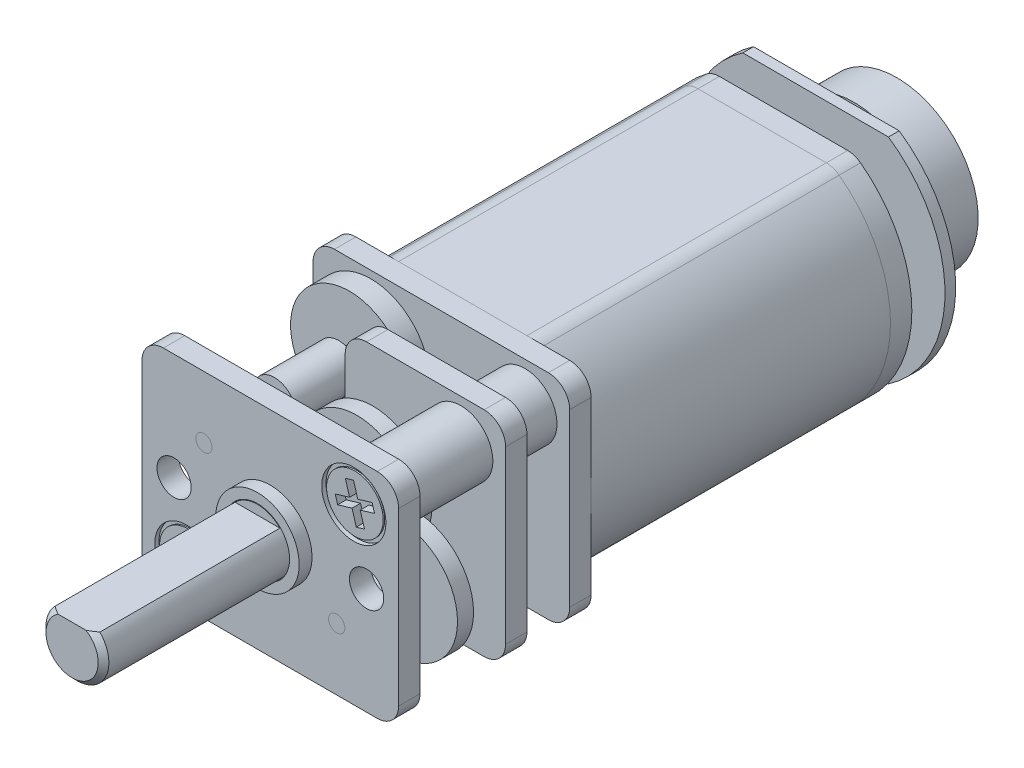
SolidWorks part; units mm, degrees
note: The reader was unsure of these and kept them because the rebuilt part matched: shared geometry of "Sketch2<2>", "Sketch9<3>", "Sketch12<2>", "Sketch29<3>".
material "Plain Carbon Steel"
ref_plane "Front Plane" through (0, 0, 0) normal (0, 0, 1) x (1, 0, 0)
ref_plane "Top Plane" through (0, 0, 0) normal (0, 1, 0) x (1, 0, 0)
ref_plane "Right Plane" through (0, 0, 0) normal (1, 0, 0) x (0, 0, -1)
sketch "Sketch1" plane through (0, 0, 0) normal (0, 0, 1) x (1, 0, 0)
  line L0 (3.3166, 5) -> (-3.3166, 5)
  line L1 (-3.3166, -5) -> (3.3166, -5)
  arc A0 (3.3166, -5) -> (3.3166, 5) centre (0, 0) ccw
  arc A1 (-3.3166, 5) -> (-3.3166, -5) centre (0, 0) ccw
  dimension "D1" = 12
  dimension "D2" = 10
extrude "Boss-Extrude1" add sketch "Sketch1" along normal mid plane 15
fillet "Fillet3" radius 1 4 edges at (-3.3166, -5, 0) (3.3166, -5, 0) (3.3166, 5, 0) (-3.3166, 5, 0)
sketch "Sketch2" plane through (0, 0, 7.5) normal (0, 0, 1) x (1, 0, 0)
  line L1 (-5, -5) -> (5, -5)
  line L2 (-6, -4) -> (-6, 4)
  line L3 (-5, 5) -> (5, 5)
  line L4 (6, -4) -> (6, 4)
  line L5 (-6, -5) -> (6, 5) construction
  line L6 (-6, 5) -> (6, -5) construction
  arc A0 (-5, -5) -> (-6, -4) centre (-5, -4) cw
  arc A1 (5, -5) -> (6, -4) centre (5, -4) ccw
  arc A2 (5, 5) -> (6, 4) centre (5, 4) cw
  arc A3 (-6, 4) -> (-5, 5) centre (-5, 4) cw
  point P0 (0, 0)
  dimension "D3" = 1
  dimension "D1" = 12
  dimension "D2" = 10
extrude "Boss-Extrude2" add sketch "Sketch2" along normal blind 1 separate body
extrude "Boss-Extrude3" add sketch "Sketch2<2>" against normal blind 1 from offset 9 separate body
sketch "Sketch2<2>" plane through (0, 0, 7.5) normal (0, 0, 1) x (1, 0, 0) same geometry as "Sketch2"
sketch "Sketch7" plane through (0, 0, 8.5) normal (0, 0, 1) x (1, 0, 0)
  line L0 (-3.1041, 2.1041) -> (3.1041, -2.1041) construction
  line L1 (0, 0) -> (0, 50000) construction
  line L2 (-6, 4) -> (-6, -4) construction
  line L3 (5, 5) -> (-5, 5) construction
  circle A0 centre (0, 0) radius 3.75 construction
  circle A1 centre (-3.1041, 2.1041) radius 0.5
  circle A2 centre (3.1041, -2.1041) radius 0.5
  circle A3 centre (-3.1041, 2.1041) radius 2.8959 construction
  point P3 (3.1041, -2.1041)
  point P4 (-3.1041, 2.1041)
  dimension "D1" = 7.5
  dimension "D3" = 1
extrude "Boss-Extrude5" add sketch "Sketch7" along normal up to surface (8 mm away) separate body up to face at (0, 0, 16.5)
sketch "Sketch11" plane through (0, 0, 8.5) normal (0, 0, 1) x (1, 0, 0)
  line L0 (-5, -1.25) -> (-2.5, -1.25)
  line L1 (-1.5, -0.25) -> (-1.5, 4)
  line L4 (-5, -5) -> (5, -5)
  line L5 (6, -4) -> (6, 4)
  line L6 (5, 5) -> (-5, 5)
  line L7 (-6, 4) -> (-6, -4)
  line L8 (-5, -5) -> (5, -5)
  line L9 (6, -4) -> (6, 4)
  line L10 (5, 5) -> (-0.5, 5)
  line L11 (-6, -2.25) -> (-6, -4)
  arc A0 (-1.5, 4) -> (-0.5, 5) centre (-0.5, 4) cw
  arc A1 (-2.5, -1.25) -> (-1.5, -0.25) centre (-2.5, -0.25) ccw
  arc A2 (-5, -1.25) -> (-6, -2.25) centre (-5, -2.25) ccw
  arc A4 (-6, -4) -> (-5, -5) centre (-5, -4) ccw
  arc A5 (5, -5) -> (6, -4) centre (5, -4) ccw
  arc A6 (6, 4) -> (5, 5) centre (5, 4) ccw
  arc A7 (-5, 5) -> (-6, 4) centre (-5, 4) ccw
  arc A8 (-6, -4) -> (-5, -5) centre (-5, -4) ccw
  arc A9 (5, -5) -> (6, -4) centre (5, -4) ccw
  arc A10 (6, 4) -> (5, 5) centre (5, 4) ccw
  dimension "D2" = 1
  dimension "D3" = 7.5
  dimension "D4" = 3.75
  dimension "D1" = 0
extrude "Boss-Extrude8" add sketch "Sketch11" along normal blind 1 from offset 2 separate body
sketch "Sketch5" plane through (0, 0, 16.5) normal (0, 0, 1) x (1, 0, 0)
  line L0 (5, 4) -> (-5, -4) construction
  circle A0 centre (0, 0) radius 0.75
  circle A1 centre (-3.1041, 2.1041) radius 0.38
  circle A2 centre (3.1041, -2.1041) radius 0.38
  circle A3 centre (0, 0) radius 5 construction
  circle A4 centre (3.9043, 3.1235) radius 0.75
  circle A5 centre (-3.9043, -3.1235) radius 0.75
  circle A6 centre (0, 0) radius 5.75 construction
  dimension "D1" = 1.5
  dimension "D2" = 0.76
  dimension "D3" = 11.5
  dimension "D4" = 1.5
extrude "Cut-Extrude1" cut sketch "Sketch5" against normal up to surface (9 mm away)
sketch "Sketch8" plane through (0, 0, 16.5) normal (0, 0, 1) x (1, 0, 0)
  circle A0 centre (-3.1041, 2.1041) radius 0.5
  circle A1 centre (3.1041, -2.1041) radius 0.5
  circle A2 centre (-3.1041, 2.1041) radius 0.5 construction
  circle A3 centre (-3.1041, 2.1041) radius 0.38
  circle A4 centre (3.1041, -2.1041) radius 0.38
  circle A5 centre (-3.1041, 2.1041) radius 0.38 construction
extrude "Cut-Extrude2" cut sketch "Sketch8" against normal blind 1
sketch "Sketch9" plane through (0, 0, 8.5) normal (0, 0, 1) x (1, 0, 0)
  circle A0 centre (-3.1041, 2.1041) radius 2.75
  circle A1 centre (-3.1041, 2.1041) radius 0.5
  circle A2 centre (-3.1041, 2.1041) radius 0.5 construction
  circle A3 centre (0, 0) radius 1
  circle M1 centre (0, 0) radius 0.75
  dimension "D1" = 5.5
  dimension "D2" = 2
extrude "Boss-Extrude6" add sketch "Sketch9" along normal blind 1 from offset 0.2 separate body contours A0 A1
extrude "Boss-Extrude16" add sketch "Sketch9<3>" along normal blind 1.3 from offset 0.1 separate body contours A3 M1 | M1
sketch "Sketch9<3>" plane through (0, 0, 8.5) normal (0, 0, 1) x (1, 0, 0) same geometry as "Sketch9"
sketch "Sketch6" plane through (0, 0, 16.5) normal (0, 0, 1) x (1, 0, 0)
  circle A0 centre (0, 0) radius 1.95
  circle A1 centre (0, 0) radius 0.75
  circle A2 centre (0, 0) radius 0.75 construction
  dimension "D1" = 3.9
extrude "Boss-Extrude4" add sketch "Sketch6" along normal blind 0.6
sketch "Sketch10" plane through (0, 0, 9.7) normal (0, 0, 1) x (1, 0, 0)
  circle A0 centre (-3.1041, 2.1041) radius 0.5
  circle A1 centre (-3.1041, 2.1041) radius 1
  circle A2 centre (0, 0) radius 2.75 construction
  circle A4 centre (-3.1041, 2.1041) radius 0.5 construction
  circle A5 centre (-3.1041, 2.1041) radius 2.75 construction
extrude "Boss-Extrude7" add sketch "Sketch10" along normal blind 3 from offset 0.5 separate body
sketch "Sketch12" plane through (0, 0, 8.5) normal (0, 0, 1) x (1, 0, 0)
  circle A0 centre (-3.9043, -3.1235) radius 0.75
  circle A1 centre (-3.9043, -3.1235) radius 1.5
  circle A2 centre (-3.9043, -3.1235) radius 0.75 construction
  circle A3 centre (3.9043, 3.1235) radius 0.75
  circle A4 centre (3.9043, 3.1235) radius 1.5
  dimension "D1" = 3
extrude "Boss-Extrude9" add sketch "Sketch12" along normal up to next (2 mm away) separate body
extrude "Boss-Extrude10" add sketch "Sketch12<2>" along normal up to next (7 mm away) from surface at 3 separate body starting at face at (0.75, 0, 11.5)
sketch "Sketch12<2>" plane through (0, 0, 8.5) normal (0, 0, 1) x (1, 0, 0) same geometry as "Sketch12"
sketch "Sketch13" plane through (0, 0, 17.1) normal (0, 0, 1) x (1, 0, 0)
  circle A0 centre (0, 0) radius 1.5
  dimension "D1" = 3
extrude "Cut-Extrude3" cut sketch "Sketch13" against normal up to next (7.2 mm away)
sketch "Sketch14" plane through (0, 0, 16.5) normal (0, 0, 1) x (1, 0, 0)
  circle A0 centre (3.9043, 3.1235) radius 1.5
  circle A1 centre (-3.9043, -3.1235) radius 1.5
  dimension "D1" = 3
extrude "Cut-Extrude4" cut sketch "Sketch14" against normal blind 0.2
chamfer "Chamfer1" distance 0.5 angle 45 2 edges at (-3.1543, -3.1235, 16.3) (4.6543, 3.1235, 16.3)
sketch "Sketch15" plane through (0, 0, 11.5) normal (0, 0, 1) x (1, 0, 0)
  circle A0 centre (0, 0) radius 2.75
  circle A1 centre (-3.1041, 2.1041) radius 1 construction
extrude "Boss-Extrude11" add sketch "Sketch15" along normal blind 0.75 from offset 0.2 separate body
sketch "Sketch16" plane through (0, 0, 12.45) normal (0, 0, 1) x (1, 0, 0)
  circle A0 centre (0, 0) radius 1
  circle A2 centre (0, 0) radius 1 construction
extrude "Boss-Extrude12" add sketch "Sketch16" along normal blind 1.15 from offset 0.2
sketch "Sketch17" plane through (0, 0, 12.45) normal (0, 0, 1) x (1, 0, 0)
  circle A0 centre (3.1041, -2.1041) radius 2.75
  circle A2 centre (0, 0) radius 1 construction
extrude "Boss-Extrude13" add sketch "Sketch17" along normal blind 0.75 from offset 0.4 separate body
sketch "Sketch18" plane through (0, 0, 13.6) normal (0, 0, 1) x (1, 0, 0)
  circle A0 centre (3.1041, -2.1041) radius 1
  circle A1 centre (0, 0) radius 1 construction
extrude "Boss-Extrude14" add sketch "Sketch18" along normal blind 1.5 from offset 0.2
sketch "Sketch19" plane through (0, 0, 15.3) normal (0, 0, 1) x (1, 0, 0)
  circle A0 centre (3.1041, -2.1041) radius 0.5
  circle A1 centre (3.1041, -2.1041) radius 0.5 construction
extrude "Cut-Extrude5" cut sketch "Sketch19" against normal through all
sketch "Sketch20" plane through (0, 0, 15.3) normal (0, 0, 1) x (1, 0, 0)
  circle A0 centre (0, 0) radius 2.75
  circle A1 centre (3.1041, -2.1041) radius 1 construction
extrude "Boss-Extrude15" add sketch "Sketch20" against normal blind 1 separate body
sketch "Sketch21" plane through (0, 0, 15.3) normal (0, 0, 1) x (1, 0, 0)
  circle A0 centre (0, 0) radius 0.5
  dimension "D1" = 1
extrude "Cut-Extrude6" cut sketch "Sketch21" against normal up to surface (7.8 mm away)
sketch "Sketch22" plane through (0, 0, 0) normal (0, 1, 0) x (1, 0, 0)
  line L0 (0, 0) -> (0, -50000) construction
  line L1 (-3, 7.5) -> (3, 7.5) construction
  line L2 (-0.5, -7.5) -> (-0.5, -15.3)
  line L3 (0.75, -7.5) -> (-0.75, -7.5) construction
  line L4 (-0.5, -15.3) -> (0.5, -15.3) construction
  line L5 (-0.5, -15.3) -> (-1.47, -15.3)
  line L6 (-2.75, -15.3) -> (2.75, -15.3) construction
  line L7 (-1.47, -15.3) -> (-1.47, -25.77)
  line L8 (-1.47, -25.77) -> (0, -25.77)
  line L9 (0, -25.77) -> (0, -7.5)
  line L10 (3, -7.5) -> (-3, -7.5) construction
  line L11 (0, -7.5) -> (-0.5, -7.5)
  line L12 (5, -16.5) -> (-5, -16.5) construction
  point P4 (0, 7.5)
  dimension "D1" = 1
  dimension "D2" = 2.94
  dimension "D3" = 9.27
revolve "Revolve1" add sketch "Sketch22" angle 360 about L0
chamfer "Chamfer2" distance 0.25 angle 45 1 edges at (-1.47, 0, 25.77)
sketch "Sketch23" plane through (0, 0, 25.77) normal (0, 0, 1) x (1, 0, 0)
  line L0 (1.0488, 1.03) -> (-1.0488, 1.03)
  circle A0 centre (0, 0) radius 1.47 construction
  arc A1 (1.0488, 1.03) -> (-1.0488, 1.03) centre (0, 0) ccw
  point P4 (0, -1.47)
  dimension "D1" = 2.5
extrude "Cut-Extrude7" cut sketch "Sketch23" against normal up to surface (8.67 mm away) up to face at (1.5, 0, 17.1)
sketch "Sketch24" plane through (0, 0, 16.5) normal (0, 0, 1) x (1, 0, 0)
  circle A0 centre (4.5, 0) radius 0.8
  circle A1 centre (-4.5, 0) radius 0.8
  dimension "D3" = 1.6
  dimension "D1" = 4.5
  dimension "D2" = 9
extrude "Cut-Extrude8" cut sketch "Sketch24" against normal up to next (1 mm away)
sketch "Sketch25" plane through (0, 0, -7.5) normal (0, 0, -1) x (-1, 0, 0)
  line L2 (-3, -5) -> (3, -5)
  line L3 (3, 5) -> (-3, 5)
  line L4 (-3, -5) -> (3, -5)
  line L5 (3, 5) -> (-3, 5)
  arc A2 (-3.6, 4.8) -> (-3.6, -4.8) centre (0, 0) ccw
  arc A3 (3.6, -4.8) -> (3.6, 4.8) centre (0, 0) ccw
  arc A4 (-3.6, 4.8) -> (-3.6, -4.8) centre (0, 0) ccw
  arc A5 (3.6, -4.8) -> (3.6, 4.8) centre (0, 0) ccw
  arc A10 (3, -5) -> (3.6, -4.8) centre (3, -4) ccw
  arc A11 (3, -5) -> (3.6, -4.8) centre (3, -4) ccw
  arc A12 (3.6, 4.8) -> (3, 5) centre (3, 4) ccw
  arc A13 (3.6, 4.8) -> (3, 5) centre (3, 4) ccw
  arc A14 (-3, 5) -> (-3.6, 4.8) centre (-3, 4) ccw
  arc A15 (-3, 5) -> (-3.6, 4.8) centre (-3, 4) ccw
  arc A16 (-3.6, -4.8) -> (-3, -5) centre (-3, -4) ccw
  arc A17 (-3.6, -4.8) -> (-3, -5) centre (-3, -4) ccw
  dimension "D1" = 0
extrude "Cut-Extrude9" cut sketch "Sketch25" against normal blind 1
sketch "Sketch26" plane through (0, 0, -6.5) normal (0, 0, -1) x (-1, 0, 0)
  line L2 (-3, -5) -> (3, -5)
  line L3 (3, 5) -> (-3, 5)
  line L4 (-3, -5) -> (3, -5)
  line L5 (3, 5) -> (-3, 5)
  arc A2 (-3.6, 4.8) -> (-3.6, -4.8) centre (0, 0) ccw
  arc A3 (3.6, -4.8) -> (3.6, 4.8) centre (0, 0) ccw
  arc A4 (-3.6, 4.8) -> (-3.6, -4.8) centre (0, 0) ccw
  arc A5 (3.6, -4.8) -> (3.6, 4.8) centre (0, 0) ccw
  arc A10 (-3.6, -4.8) -> (-3, -5) centre (-3, -4) ccw
  arc A11 (-3.6, -4.8) -> (-3, -5) centre (-3, -4) ccw
  arc A12 (3, -5) -> (3.6, -4.8) centre (3, -4) ccw
  arc A13 (3, -5) -> (3.6, -4.8) centre (3, -4) ccw
  arc A14 (3.6, 4.8) -> (3, 5) centre (3, 4) ccw
  arc A15 (3.6, 4.8) -> (3, 5) centre (3, 4) ccw
  arc A16 (-3, 5) -> (-3.6, 4.8) centre (-3, 4) ccw
  arc A17 (-3, 5) -> (-3.6, 4.8) centre (-3, 4) ccw
  dimension "D1" = 0
extrude "Boss-Extrude17" add sketch "Sketch26" along normal blind 1 separate body
sketch "Sketch27" plane through (0, 0, -7.5) normal (0, 0, -1) x (-1, 0, 0)
  circle A0 centre (0, 0) radius 2.5
  dimension "D1" = 5
extrude "Boss-Extrude18" add sketch "Sketch27" along normal blind 1.5
sketch "Sketch28" plane through (0, 0, -7.5) normal (0, 0, -1) x (-1, 0, 0)
  line L1 (3.35, 0.75) -> (3.65, 0.75)
  line L2 (3.35, 0.75) -> (3.35, -0.75)
  line L3 (3.35, -0.75) -> (3.65, -0.75)
  line L4 (3.65, 0.75) -> (3.65, -0.75)
  line L5 (3.35, 0.75) -> (3.65, -0.75) construction
  line L6 (3.35, -0.75) -> (3.65, 0.75) construction
  line L7 (-3.65, 0.75) -> (-3.35, 0.75)
  line L8 (-3.65, 0.75) -> (-3.65, -0.75)
  line L9 (-3.65, -0.75) -> (-3.35, -0.75)
  line L10 (-3.35, 0.75) -> (-3.35, -0.75)
  line L11 (-3.65, 0.75) -> (-3.35, -0.75) construction
  line L12 (-3.65, -0.75) -> (-3.35, 0.75) construction
  point P0 (3.5, 0)
  point P5 (-3.5, 0)
  dimension "D1" = 3.5
  dimension "D2" = 7
  dimension "D3" = 0.3
  dimension "D4" = 1.5
extrude "Boss-Extrude19" add sketch "Sketch28" along normal blind 2 separate body
fillet "Fillet1" radius 0.7 2 edges at (-3.5, -0.75, -9.5) (-3.5, 0.75, -9.5)
fillet "Fillet2" radius 0.7 2 edges at (3.5, -0.75, -9.5) (3.5, 0.75, -9.5)
ref_plane "Plane1" through (0, 0, 0) normal (0.6247, -0.7809, 0) x (0.7809, 0.6247, 0)
sketch "Sketch29" plane through (0, 0, 0) normal (0.6247, -0.7809, 0) x (0.7809, 0.6247, 0)
  line L0 (5, 16.5) -> (5, 50016.5) construction
  line L1 (6.5, 16.5) -> (3.5, 16.5) construction
  line L2 (-5, 16.5) -> (-5, 50016.5) construction
  line L3 (-3.5, 16.5) -> (-6.5, 16.5) construction
  line L4 (5.7, 7.5) -> (5.7, 15.755)
  line L5 (6, 7.5) -> (-0.1874, 7.5) construction
  line L6 (5.7, 15.755) -> (6.325, 16.38)
  line L7 (6.325, 16.38) -> (6.325, 16.45)
  line L8 (6.325, 16.45) -> (5, 16.45)
  line L9 (5, 16.45) -> (5, 7.5)
  line L10 (4.25, 7.5) -> (5.75, 7.5) construction
  line L11 (5, 7.5) -> (5.7, 7.5)
  line L12 (2.1864, 16.5) -> (7.184, 16.5) construction
  line L13 (0, 0) -> (0, 50000) construction
  line L14 (-5, 7.5) -> (-5.7, 7.5)
  line L15 (-5, 16.45) -> (-5, 7.5)
  line L16 (-6.325, 16.45) -> (-5, 16.45)
  line L17 (-6.325, 16.38) -> (-6.325, 16.45)
  line L18 (-5.7, 15.755) -> (-6.325, 16.38)
  line L19 (-5.7, 7.5) -> (-5.7, 15.755)
  point P4 (5, 16.5)
  point P9 (-5, 16.5)
  dimension "D1" = 45
  dimension "D2" = 1.4
  dimension "D3" = 2.65
  dimension "D4" = 0.05
  dimension "D5" = 0.07
revolve "Revolve2" add sketch "Sketch29" angle 360 about L0
revolve "Revolve3" add sketch "Sketch29<3>" angle 360 about L2
sketch "Sketch29<3>" plane through (0, 0, 0) normal (0.6247, -0.7809, 0) x (0.7809, 0.6247, 0) same geometry as "Sketch29"
sketch "Sketch30" plane through (0, 0, 16.45) normal (0, 0, 1) x (1, 0, 0)
  line L0 (-3.5871, -2.2813) -> (-4.2216, -3.9657) construction
  line L1 (-3.7742, -2.2107) -> (-4.021, -2.8658)
  line L2 (-4.7466, -2.8062) -> (-3.0621, -3.4408) construction
  line L3 (-4.8171, -2.9934) -> (-4.162, -3.2401)
  line L4 (-3.3999, -2.3518) -> (-3.6467, -3.0068)
  line L5 (-4.6761, -2.619) -> (-4.021, -2.8658)
  line L6 (-3.7742, -2.2107) -> (-3.3999, -2.3518)
  line L7 (-4.4088, -3.8952) -> (-4.0345, -4.0362)
  line L8 (-4.8171, -2.9934) -> (-4.6761, -2.619)
  line L9 (-3.1326, -3.6279) -> (-2.9916, -3.2536)
  line L10 (-4.162, -3.2401) -> (-4.4088, -3.8952)
  line L11 (-3.7742, -2.2107) -> (-4.4088, -3.8952) construction
  line L12 (-3.6467, -3.0068) -> (-2.9916, -3.2536)
  line L13 (-4.6761, -2.619) -> (-2.9916, -3.2536) construction
  line L14 (-3.7877, -3.3811) -> (-4.0345, -4.0362)
  line L15 (-3.3999, -2.3518) -> (-4.0345, -4.0362) construction
  line L16 (-3.7877, -3.3811) -> (-3.1326, -3.6279)
  line L17 (-4.8171, -2.9934) -> (-3.1326, -3.6279) construction
  line L18 (3.6482, 3.9863) -> (4.1605, 2.2607) construction
  line L19 (3.0416, 2.8674) -> (4.7671, 3.3796) construction
  line L20 (3.4565, 3.9293) -> (3.6557, 3.2583)
  line L21 (3.0985, 2.6756) -> (3.7695, 2.8748)
  line L22 (3.84, 4.0432) -> (4.0392, 3.3721)
  line L23 (2.9846, 3.0591) -> (3.6557, 3.2583)
  line L24 (3.4565, 3.9293) -> (3.84, 4.0432)
  line L25 (3.9687, 2.2038) -> (4.3522, 2.3176)
  line L26 (3.0985, 2.6756) -> (2.9846, 3.0591)
  line L27 (4.824, 3.1879) -> (4.7102, 3.5713)
  line L28 (4.0392, 3.3721) -> (4.7102, 3.5713)
  line L29 (2.9846, 3.0591) -> (4.7102, 3.5713) construction
  line L30 (3.7695, 2.8748) -> (3.9687, 2.2038)
  line L31 (3.4565, 3.9293) -> (3.9687, 2.2038) construction
  line L32 (4.153, 2.9887) -> (4.824, 3.1879)
  line L33 (3.0985, 2.6756) -> (4.824, 3.1879) construction
  line L34 (4.153, 2.9887) -> (4.3522, 2.3176)
  line L35 (3.84, 4.0432) -> (4.3522, 2.3176) construction
  point P2 (-3.9043, -3.1235)
  point P15 (3.9043, 3.1235)
  dimension "D1" = 1.8
  dimension "D2" = 0.2
  dimension "D3" = 0.2
  dimension "D4" = 0.2
  dimension "D5" = 0.2
extrude "Cut-Extrude10" cut sketch "Sketch30" against normal blind 0.4
sketch "Sketch31" plane through (0, 0, -9) normal (0, 0, -1) x (-1, 0, 0)
  circle A0 centre (0, 0) radius 0.5
  dimension "D1" = 1
extrude "Boss-Extrude20" add sketch "Sketch31" along normal blind 4 separate body
sketch "Sketch32" plane through (0, 0, -9) normal (0, 0, -1) x (-1, 0, 0)
  line L0 (-3.4062, -5) -> (3.4062, -5)
  line L2 (-3.4062, 5) -> (3.4062, 5)
  circle A0 centre (0, 0) radius 6.05
  circle A1 centre (0, 0) radius 0.6102
  point P6 (0, -5)
  point P9 (0, 5)
  circle M1 centre (0, 0) radius 2.5
  dimension "D1" = 12.1
extrude "Boss-Extrude21" add sketch "Sketch32" along normal blind 0.5 separate body contours L2 A0 L0 M1 | M1
ref_plane "Plane2" through (0, 0, -10.8) normal (0, 0, -1) x (-1, 0, 0)
sketch "Sketch33" plane through (0, 0, -10.8) normal (0, 0, -1) x (-1, 0, 0)
  circle A0 centre (0, 0) radius 3.8
  dimension "D1" = 7.6
extrude "Boss-Extrude22" add sketch "Sketch33" along normal blind 2 separate body
